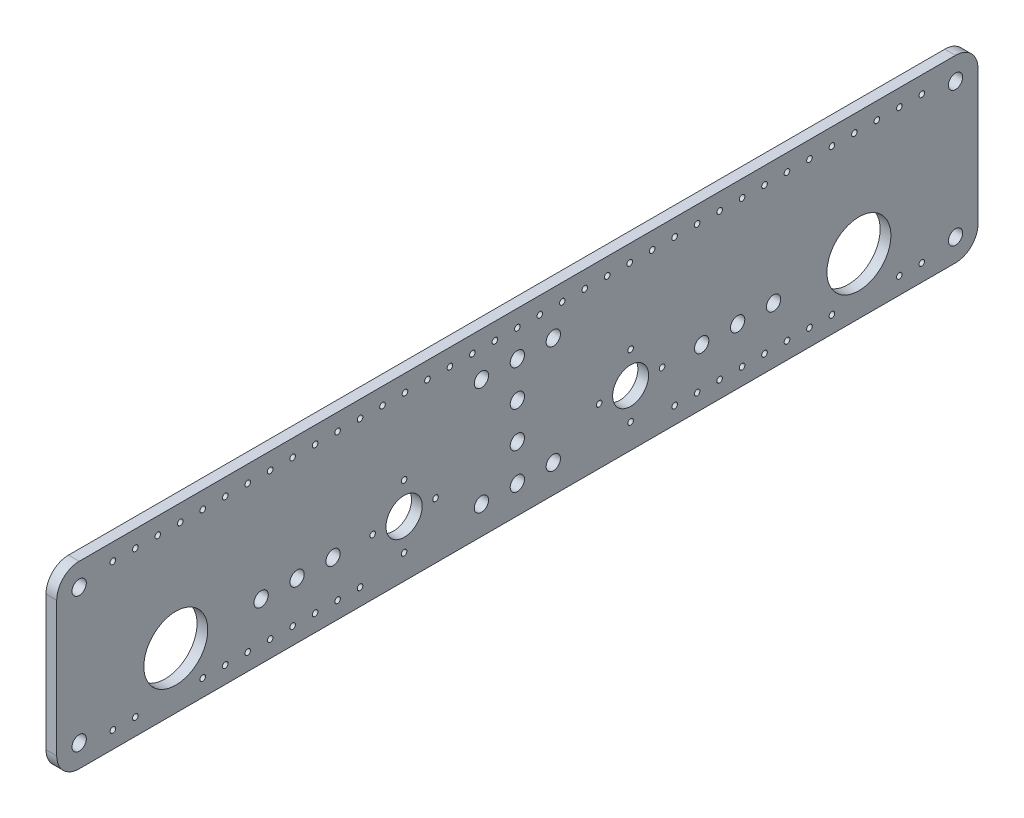
SolidWorks part; units mm, degrees
ref_plane "Front Plane" through (0, 0, 0) normal (0, 0, 1) x (1, 0, 0)
ref_plane "Top Plane" through (0, 0, 0) normal (0, 1, 0) x (1, 0, 0)
ref_plane "Right Plane" through (0, 0, 0) normal (1, 0, 0) x (0, 0, -1)
sketch "Sketch2" plane through (0, 0, 0) normal (1, 0, 0) x (0, 0, -1)
  line L0 (-23.4723, 28.6683) -> (-23.4723, -31.3317)
  line L1 (-13.4723, 38.6683) -> (376.5277, 38.6683)
  line L2 (-13.4723, -41.3317) -> (376.5277, -41.3317)
  line L3 (386.5277, 28.6683) -> (386.5277, -31.3317)
  circle A1 centre (29.5277, -16.3317) radius 14.225
  circle A2 centre (333.5277, -16.3317) radius 14.225
  arc A15 (-23.4723, 28.6683) -> (-13.4723, 38.6683) centre (-13.4723, 28.6683) cw
  arc A16 (-13.4723, -41.3317) -> (-23.4723, -31.3317) centre (-13.4723, -31.3317) cw
  arc A17 (386.5277, 28.6683) -> (376.5277, 38.6683) centre (376.5277, 28.6683) ccw
  arc A18 (376.5277, -41.3317) -> (386.5277, -31.3317) centre (376.5277, -31.3317) ccw
  circle A59 centre (181.5277, -28.7717) radius 3.18
  circle A60 centre (197.5277, -28.7717) radius 3.18
  circle A63 centre (197.5277, 19.2283) radius 3.18
  circle A64 centre (181.5277, -12.7717) radius 3.18
  circle A65 centre (181.5277, 3.2283) radius 3.18
  circle A66 centre (181.5277, 19.2283) radius 3.18
  circle A67 centre (165.5277, -28.7717) radius 3.18
  circle A68 centre (165.5277, 19.2283) radius 3.18
  circle A69 centre (197.5277, -12.7717) radius 3.18 [skipped]
  circle A70 centre (197.5277, 3.2283) radius 3.18 [skipped]
  circle A71 centre (-8.4723, 31.1683) radius 1.25 construction
  circle A150 centre (83.5027, -16.3317) radius 3.18
  circle A151 centre (279.5527, -16.3317) radius 3.18
  circle A152 centre (1.5277, 31.1683) radius 1.25
  circle A153 centre (11.5277, 31.1683) radius 1.25
  circle A154 centre (21.5277, 31.1683) radius 1.25
  circle A155 centre (31.5277, 31.1683) radius 1.25
  circle A156 centre (41.5277, 31.1683) radius 1.25
  circle A157 centre (51.5277, 31.1683) radius 1.25
  circle A158 centre (61.5277, 31.1683) radius 1.25
  circle A159 centre (71.5277, 31.1683) radius 1.25
  circle A160 centre (81.5277, 31.1683) radius 1.25
  circle A161 centre (91.5277, 31.1683) radius 1.25
  circle A162 centre (101.5277, 31.1683) radius 1.25
  circle A163 centre (111.5277, 31.1683) radius 1.25
  circle A164 centre (121.5277, 31.1683) radius 1.25
  circle A165 centre (131.5277, 31.1683) radius 1.25
  circle A166 centre (141.5277, 31.1683) radius 1.25
  circle A167 centre (151.5277, 31.1683) radius 1.25
  circle A168 centre (161.5277, 31.1683) radius 1.25
  circle A169 centre (171.5277, 31.1683) radius 1.25
  circle A170 centre (181.5277, 31.1683) radius 1.25
  circle A171 centre (191.5277, 31.1683) radius 1.25
  circle A172 centre (201.5277, 31.1683) radius 1.25
  circle A173 centre (211.5277, 31.1683) radius 1.25
  circle A174 centre (221.5277, 31.1683) radius 1.25
  circle A175 centre (231.5277, 31.1683) radius 1.25
  circle A176 centre (241.5277, 31.1683) radius 1.25
  circle A177 centre (251.5277, 31.1683) radius 1.25
  circle A178 centre (261.5277, 31.1683) radius 1.25
  circle A179 centre (271.5277, 31.1683) radius 1.25
  circle A180 centre (281.5277, 31.1683) radius 1.25
  circle A181 centre (291.5277, 31.1683) radius 1.25
  circle A182 centre (301.5277, 31.1683) radius 1.25
  circle A183 centre (311.5277, 31.1683) radius 1.25
  circle A184 centre (321.5277, 31.1683) radius 1.25
  circle A185 centre (331.5277, 31.1683) radius 1.25
  circle A186 centre (341.5277, 31.1683) radius 1.25
  circle A187 centre (351.5277, 31.1683) radius 1.25
  circle A188 centre (361.5277, 31.1683) radius 1.25
  circle A190 centre (1.5277, -33.8317) radius 1.25
  circle A191 centre (11.5277, -33.8317) radius 1.25
  circle A194 centre (41.5277, -33.8317) radius 1.25
  circle A195 centre (51.5277, -33.8317) radius 1.25
  circle A196 centre (61.5277, -33.8317) radius 1.25
  circle A197 centre (71.5277, -33.8317) radius 1.25
  circle A198 centre (81.5277, -33.8317) radius 1.25
  circle A199 centre (91.5277, -33.8317) radius 1.25
  circle A200 centre (101.5277, -33.8317) radius 1.25
  circle A201 centre (111.5277, -33.8317) radius 1.25
  circle A215 centre (251.5277, -33.8317) radius 1.25
  circle A216 centre (261.5277, -33.8317) radius 1.25
  circle A217 centre (271.5277, -33.8317) radius 1.25
  circle A218 centre (281.5277, -33.8317) radius 1.25
  circle A219 centre (291.5277, -33.8317) radius 1.25
  circle A220 centre (301.5277, -33.8317) radius 1.25
  circle A221 centre (311.5277, -33.8317) radius 1.25
  circle A222 centre (321.5277, -33.8317) radius 1.25
  circle A225 centre (351.5277, -33.8317) radius 1.25
  circle A226 centre (361.5277, -33.8317) radius 1.25
  circle A229 centre (181.5277, -33.8317) radius 1.25 [skipped]
  circle A230 centre (201.5277, -33.8317) radius 1.25 [skipped]
  circle A231 centre (161.5277, -33.8317) radius 1.25 [skipped]
  circle A232 centre (151.5277, -33.8317) radius 1.25 [skipped]
  circle A233 centre (141.5277, -33.8317) radius 1.25 [skipped]
  circle A234 centre (131.5277, -33.8317) radius 1.25 [skipped]
  circle A235 centre (171.5277, -33.8317) radius 1.25 [skipped]
  circle A236 centre (191.5277, -33.8317) radius 1.25 [skipped]
  circle A237 centre (211.5277, -33.8317) radius 1.25 [skipped]
  circle A238 centre (221.5277, -33.8317) radius 1.25 [skipped]
  circle A239 centre (231.5277, -33.8317) radius 1.25 [skipped]
  circle A240 centre (31.5277, -33.8317) radius 1.25 [skipped]
  circle A241 centre (21.5277, -33.8317) radius 1.25 [skipped]
  circle A242 centre (331.5277, -33.8317) radius 1.25 [skipped]
  circle A243 centre (341.5277, -33.8317) radius 1.25 [skipped]
  circle A244 centre (-13.4723, -31.3317) radius 3.18
  circle A245 centre (-13.4723, 28.6683) radius 3.18
  circle A246 centre (376.5277, -31.3317) radius 3.18
  circle A247 centre (376.5277, 28.6683) radius 3.18
  circle A248 centre (371.5277, 31.1683) radius 1.25 [skipped]
  circle A249 centre (371.5277, -33.8317) radius 1.25 [skipped]
  circle A250 centre (-8.4723, -33.8317) radius 1.25 [skipped]
  circle A253 centre (99.5027, -16.3317) radius 3.18
  circle A254 centre (295.5527, -16.3317) radius 3.18
  circle A255 centre (67.5027, -16.3317) radius 3.18
  circle A256 centre (263.5527, -16.3317) radius 3.18
  circle A257 centre (121.5277, -33.8317) radius 1.25 [skipped]
  circle A260 centre (131.1277, -30.3317) radius 1.25
  circle A261 centre (145.1277, -16.3317) radius 1.25
  circle A262 centre (131.1277, -2.3317) radius 1.25
  circle A263 centre (117.1277, -16.3317) radius 1.25
  circle A264 centre (231.9277, -30.3317) radius 1.25
  circle A265 centre (217.9277, -16.3317) radius 1.25
  circle A266 centre (231.9277, -2.3317) radius 1.25
  circle A267 centre (245.9277, -16.3317) radius 1.25
  circle A268 centre (231.9277, -16.3317) radius 8
  circle A269 centre (131.1277, -16.3317) radius 8.0683
  circle A270 centre (241.5277, -33.8317) radius 1.25 [skipped]
  point P32 (-23.4723, 38.6683)
  point P35 (-23.4723, -41.3317)
  point P40 (386.5277, -41.3317)
  point P123 (181.5277, -41.3317)
  point P125 (0, 0)
  dimension "D3" = 25
  dimension "D7" = 10
  dimension "D8" = 10
  dimension "D9" = 10
  dimension "D10" = 10
  dimension "D11" = 7.5
  dimension "D13" = 12.56
  dimension "D1" = 80
  dimension "D2" = 410
  dimension "D4" = 53
  dimension "D5" = 25
  dimension "D6" = 53
  dimension "D12" = 15
  dimension "D14" = 205
  dimension "D15" = 2
  dimension "D16" = 4
  dimension "D17" = 2
  dimension "D18" = 39
  dimension "D19" = 2
  dimension "D22" = 2
  dimension "D23" = 2
extrude "Boss-Extrude1" add sketch "Sketch2" along normal blind 4.7625
